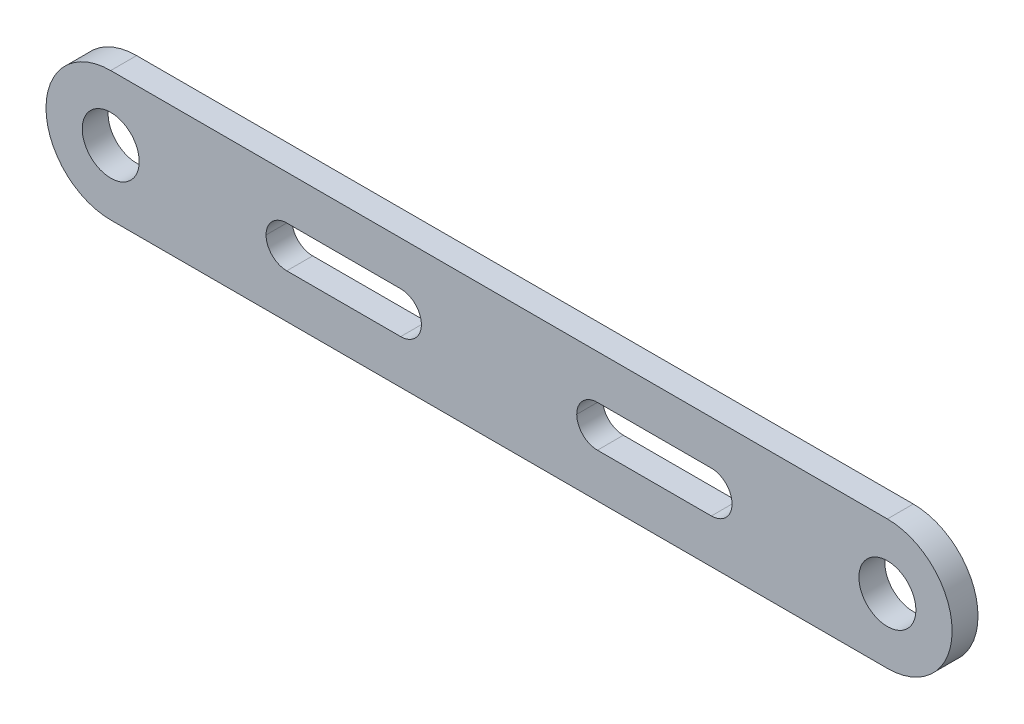
SolidWorks part; units mm, degrees
ref_plane "Front Plane" through (0, 0, 0) normal (0, 0, 1) x (1, 0, 0)
ref_plane "Top Plane" through (0, 0, 0) normal (0, 1, 0) x (1, 0, 0)
ref_plane "Right Plane" through (0, 0, 0) normal (1, 0, 0) x (0, 0, -1)
sketch "Sketch1" plane through (0, 0, 0) normal (0, 0, 1) x (1, 0, 0)
  line L5 (0, 0) -> (-91.8904, 0) construction
  line L6 (0, 33.5501) -> (0, -28.3202) construction
  line L7 (75, 12.5) -> (-75, 12.5)
  line L8 (75, -12.5) -> (-75, -12.5)
  circle A4 centre (-75, 0) radius 5.5
  arc A13 (-75, 12.5) -> (-75, -12.5) centre (-75, 0) ccw
  circle A14 centre (75, 0) radius 5.5
  arc A15 (75, 12.5) -> (75, -12.5) centre (75, 0) cw
  point P0 (0, 0)
  dimension "D3" = 12.5
  dimension "D6" = 11
  dimension "D11" = 75
extrude "Boss-Extrude1" add sketch "Sketch1" along normal blind 5
sketch "Sketch2" plane through (0, 0, 0) normal (0, 0, -1) x (-1, 0, 0)
  line L1 (-45, 4) -> (-15, 4)
  line L2 (-45, 4) -> (-45, -4)
  line L3 (-45, -4) -> (-15, -4)
  line L4 (-15, 4) -> (-15, -4)
  line L5 (15, 4) -> (45, 4)
  line L6 (15, 4) -> (15, -4)
  line L7 (15, -4) -> (45, -4)
  line L8 (45, 4) -> (45, -4)
  line L9 (-61.9874, 0) -> (58.0949, 0) construction
  dimension "D1" = 15
  dimension "D2" = 30
  dimension "D3" = 15
  dimension "D4" = 30
  dimension "D5" = 4
  dimension "D6" = 8
  dimension "D7" = 4
  dimension "D8" = 8
extrude "Cut-Extrude1" cut sketch "Sketch2" against normal blind 10
fillet "Fillet1" radius 4 8 edges at (15, -4, 2.5) (45, -4, 2.5) (45, 4, 2.5) (15, 4, 2.5) (-45, -4, 2.5) (-15, -4, 2.5) (-15, 4, 2.5) (-45, 4, 2.5)
